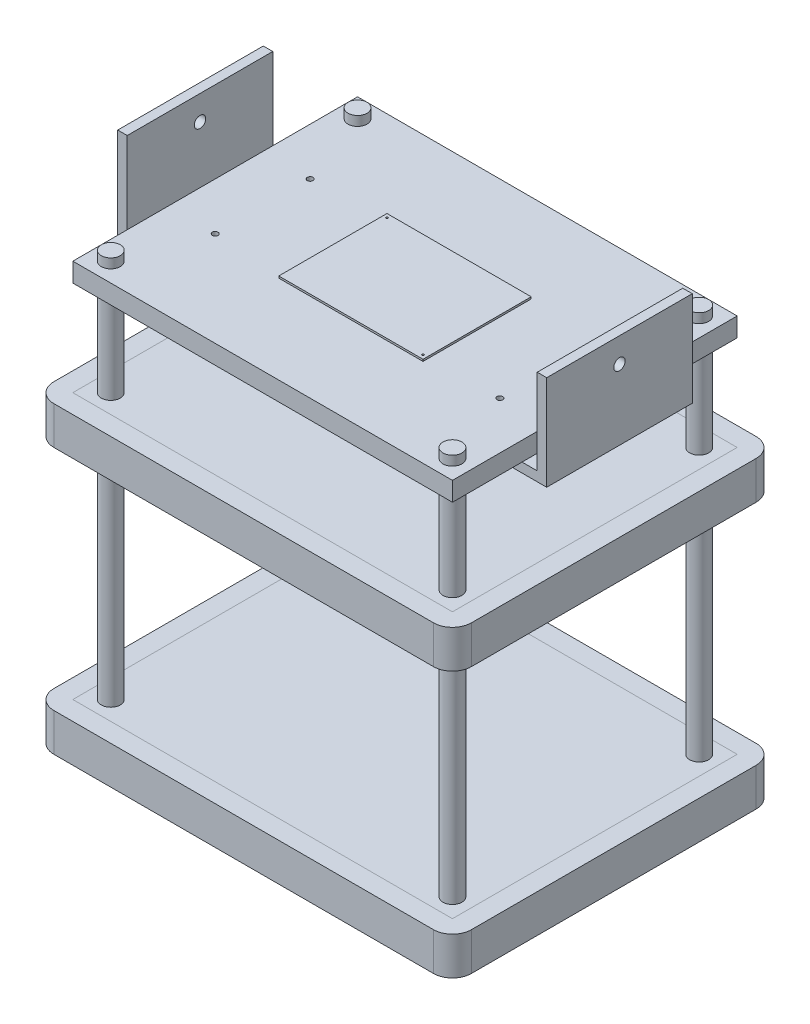
SolidWorks part; units mm, degrees
ref_plane "Front Plane" through (0, 0, 0) normal (0, 0, 1) x (1, 0, 0)
ref_plane "Top Plane" through (0, 0, 0) normal (0, 1, 0) x (1, 0, 0)
ref_plane "Right Plane" through (0, 0, 0) normal (1, 0, 0) x (0, 0, -1)
sketch "Sketch1" plane through (0, 0, 0) normal (0, 1, 0) x (1, 0, 0)
  line L1 (-100, 75) -> (100, 75)
  line L2 (-100, 75) -> (-100, -75)
  line L3 (-100, -75) -> (100, -75)
  line L4 (100, 75) -> (100, -75)
  line L5 (-100, 75) -> (100, -75) construction
  line L6 (-100, -75) -> (100, 75) construction
  point P0 (0, 0)
  dimension "D1" = 200
  dimension "D2" = 150
extrude "Boss-Extrude1" add sketch "Sketch1" along normal blind 10
sketch "Sketch2" plane through (0, 10, 0) normal (0, 1, 0) x (1, 0, 0)
  line L0 (-100, 75) -> (-100, -75) construction
  line L1 (100, 75) -> (-100, 75) construction
  line L2 (0, 73.0671) -> (0, 83.6614) construction
  line L3 (0, 83.6614) -> (0, -94.4748) construction
  line L4 (-110.8687, 0) -> (113.9791, 0) construction
  circle A0 centre (-90, 65) radius 5
  circle A1 centre (90, 65) radius 5
  circle A2 centre (90, -65) radius 5
  circle A3 centre (-90, -65) radius 5
  dimension "D1" = 10
  dimension "D2" = 10
  dimension "D3" = 10
extrude "Cut-Extrude1" cut sketch "Sketch2" against normal blind 10
ref_plane "Plane1" through (0, 140, 0) normal (0, 1, 0) x (1, 0, 0)
sketch "Sketch3" plane through (0, 140, 0) normal (0, 1, 0) x (1, 0, 0)
  line L1 (-100, 75) -> (100, 75)
  line L2 (-100, 75) -> (-100, -75)
  line L3 (-100, -75) -> (100, -75)
  line L4 (100, 75) -> (100, -75)
  line L5 (-100, 75) -> (100, -75) construction
  line L6 (-100, -75) -> (100, 75) construction
  circle A0 centre (-90, 65) radius 5
  circle A1 centre (90, 65) radius 5
  circle A2 centre (-90, -65) radius 5
  circle A3 centre (90, -65) radius 5
  point P0 (0, 0)
extrude "Boss-Extrude2" add sketch "Sketch3" along normal blind 10 separate body
ref_plane "Plane4" through (0, 200, 0) normal (0, 1, 0) x (1, 0, 0)
sketch "Sketch4" plane through (0, 200, 0) normal (0, 1, 0) x (1, 0, 0)
  line L1 (-100, 75) -> (100, 75)
  line L2 (-100, 75) -> (-100, -75)
  line L3 (-100, -75) -> (100, -75)
  line L4 (100, 75) -> (100, -75)
  line L5 (-100, 75) -> (100, -75) construction
  line L6 (-100, -75) -> (100, 75) construction
  circle A0 centre (-90, 65) radius 5
  circle A1 centre (90, 65) radius 5
  circle A2 centre (90, -65) radius 5
  circle A3 centre (-90, -65) radius 5
  point P1 (0, 0)
extrude "Boss-Extrude3" add sketch "Sketch4" along normal blind 10 separate body
sketch "Sketch5" plane through (0, 210, 0) normal (0, 1, 0) x (1, 0, 0)
  circle A0 centre (-90, -65) radius 5
sketch "Sketch17" plane through (0, 200, 0) normal (0, -1, 0) x (1, 0, 0)
  circle A0 centre (-90, -65) radius 5.3637
sketch "Sketch21" plane through (0, 10, 0) normal (0, 1, 0) x (1, 0, 0)
  circle A0 centre (-90, -65) radius 5
  circle A1 centre (-90, 65) radius 5
  circle A2 centre (90, 65) radius 5
  circle A3 centre (90, -65) radius 5
  dimension "D1" = 10
  dimension "D2" = 10
  dimension "D3" = 10
  dimension "D4" = 10
extrude "Boss-Extrude13" add sketch "Sketch21" along normal blind 205
sketch "Sketch22" plane through (0, 10, 0) normal (0, 1, 0) x (1, 0, 0)
  circle A0 centre (-90, 65) radius 5
  circle A1 centre (-90, -65) radius 5
  circle A2 centre (90, -65) radius 5
  circle A3 centre (90, 65) radius 5
  dimension "D1" = 10
  dimension "D2" = 10
  dimension "D3" = 10
  dimension "D4" = 10
extrude "Boss-Extrude14" add sketch "Sketch22" against normal blind 15
sketch "Sketch23" plane through (0, 210, 0) normal (0, 1, 0) x (1, 0, 0)
  line L0 (-100, 75) -> (-100, -75) construction
  line L1 (-140.155, 0) -> (119.4256, 0) construction
  line L2 (0, -82.5) -> (0, 82.5) construction
  circle A0 centre (-75, 25) radius 1.5
  circle A1 centre (-75, -25) radius 1.5
  circle A2 centre (75, -25) radius 1.5
  circle A3 centre (75, 25) radius 1.5
  dimension "D1" = 3
  dimension "D2" = 25
  dimension "D3" = 25
extrude "Cut-Extrude2" cut sketch "Sketch23" against normal blind 10
sketch "Sketch27" plane through (0, 210, 0) normal (0, 1, 0) x (1, 0, 0)
  line L0 (-38, 28.5) -> (38, -28.5) construction
  line L5 (-38, -28.5) -> (38, 28.5) construction
  line L7 (-38, 28.5) -> (38, 28.5)
  line L8 (-38, 28.5) -> (-38, -28.5)
  line L9 (-38, -28.5) -> (38, -28.5)
  line L10 (38, 28.5) -> (38, -28.5)
  circle A0 centre (-36, 26.5) radius 0.5
  circle A1 centre (36, -26.5) radius 0.5
  point P0 (-6.164, -10.787)
  point P5 (0, 0)
  point P11 (0, 0)
  dimension "D3" = 1
  dimension "D6" = 1
  dimension "D1" = 57
  dimension "D2" = 76
  dimension "D4" = 2
  dimension "D5" = 2
  dimension "D7" = 2
  dimension "D8" = 2
extrude "Boss-Extrude16" add sketch "Sketch27" along normal blind 1 contours L8 L7 L10 L9
sketch "Sketch30" plane through (0, 211, 0) normal (0, 1, 0) x (1, 0, 0)
  line L0 (-38, 28.5) -> (-38, -28.5) construction
  line L1 (-38, 28.5) -> (38, 28.5) construction
  line L2 (38, 28.5) -> (38, -28.5) construction
  line L3 (-38, -28.5) -> (38, -28.5) construction
  circle A0 centre (-36, 26.5) radius 0.5
  circle A1 centre (36, -26.5) radius 0.5
  dimension "D1" = 1
  dimension "D4" = 1
  dimension "D2" = 2
  dimension "D3" = 2
  dimension "D5" = 2
  dimension "D6" = 2
extrude "Cut-Extrude3" cut sketch "Sketch30" against normal blind 30
sketch "Sketch35" plane through (0, 0, 0) normal (0, -1, 0) x (-1, 0, 0)
  line L1 (100, -75) -> (-100, -75)
  line L2 (100, -75) -> (100, 75)
  line L3 (100, 75) -> (-100, 75)
  line L4 (-100, -75) -> (-100, 75)
  line L5 (100, -75) -> (-100, 75) construction
  line L6 (100, 75) -> (-100, -75) construction
  line L7 (110, -85) -> (-110, -85)
  line L8 (110, -85) -> (110, 85)
  line L9 (110, 85) -> (-110, 85)
  line L10 (-110, -85) -> (-110, 85)
  line L11 (110, -85) -> (-110, 85) construction
  line L12 (110, 85) -> (-110, -85) construction
  point P0 (0, 0)
  point P6 (0, 0)
  dimension "D1" = 150
  dimension "D2" = 170
  dimension "D3" = 200
  dimension "D4" = 220
extrude "Boss-Extrude19" add sketch "Sketch35" along normal mid plane 20 separate body
fillet "Fillet4" radius 10 4 edges at (110, 0, 85) (110, 0, -85) (-110, 0, 85) (-110, 0, -85)
sketch "Sketch39" plane through (0, 140, 0) normal (0, -1, 0) x (1, 0, 0)
  line L1 (-100, 75) -> (100, 75)
  line L2 (-100, 75) -> (-100, -75)
  line L3 (-100, -75) -> (100, -75)
  line L4 (100, 75) -> (100, -75)
  line L5 (-100, 75) -> (100, -75) construction
  line L6 (-100, -75) -> (100, 75) construction
  line L7 (-110, 85) -> (110, 85)
  line L8 (-110, 85) -> (-110, -85)
  line L9 (-110, -85) -> (110, -85)
  line L10 (110, 85) -> (110, -85)
  line L11 (-110, 85) -> (110, -85) construction
  line L12 (-110, -85) -> (110, 85) construction
  point P0 (0, 0)
  point P6 (0, 0)
  dimension "D1" = 150
  dimension "D2" = 200
  dimension "D3" = 170
  dimension "D4" = 220
extrude "Boss-Extrude20" add sketch "Sketch39" along normal mid plane 20 separate body
fillet "Fillet5" radius 10 4 edges at (110, 140, 85) (110, 140, -85) (-110, 140, -85) (-110, 140, 85)
sketch "Sketch42" plane through (0, 200, 0) normal (0, -1, 0) x (1, 0, 0)
  line L1 (-7.5, 10) -> (7.5, 10)
  line L2 (-7.5, 10) -> (-7.5, -10)
  line L3 (-7.5, -10) -> (7.5, -10)
  line L4 (7.5, 10) -> (7.5, -10)
  line L5 (-7.5, 10) -> (7.5, -10) construction
  line L6 (-7.5, -10) -> (7.5, 10) construction
  line L7 (-70.7403, -17.1967) -> (-45.7403, -17.1967)
  line L8 (-70.7403, -17.1967) -> (-70.7403, 32.8033)
  line L9 (-70.7403, 32.8033) -> (-45.7403, 32.8033)
  line L10 (-45.7403, -17.1967) -> (-45.7403, 32.8033)
  line L11 (-70.7403, -17.1967) -> (-45.7403, 32.8033) construction
  line L12 (-70.7403, 32.8033) -> (-45.7403, -17.1967) construction
  line L13 (15.7, 23.8618) -> (59, 23.8618)
  line L14 (15.7, 23.8618) -> (15.7, -19.4382)
  line L15 (15.7, -19.4382) -> (59, -19.4382)
  line L16 (59, 23.8618) -> (59, -19.4382)
  line L17 (15.7, 23.8618) -> (59, -19.4382) construction
  line L18 (15.7, -19.4382) -> (59, 23.8618) construction
  point P0 (0, 0)
  point P6 (-58.2403, 7.8033)
  point P11 (37.35, 2.2118)
  dimension "D1" = 20
  dimension "D2" = 15
  dimension "D3" = 50
  dimension "D4" = 25
  dimension "D5" = 43.3
  dimension "D6" = 43.3
  dimension "D7" = 8.2
extrude "Boss-Extrude23" add sketch "Sketch42" along normal blind 1
sketch "Sketch46" plane through (0, 200, 0) normal (0, -1, 0) x (-1, 0, 0)
  line L0 (-196.0871, 0) -> (303.0775, 0) construction
  line L5 (100, -75) -> (100, 75) construction
  line L6 (0, 93.5) -> (0, -93.5) construction
  line L7 (-108, 38.3353) -> (-108, -38.3353)
  line L8 (78, 38.3353) -> (108, 38.3353)
  line L9 (78, 38.3353) -> (78, -38.3353)
  line L10 (78, -38.3353) -> (108, -38.3353)
  line L11 (108, 38.3353) -> (108, -38.3353)
  line L12 (78, 38.3353) -> (108, -38.3353) construction
  line L13 (78, -38.3353) -> (108, 38.3353) construction
  line L14 (-78, -38.3353) -> (-108, -38.3353)
  line L15 (-78, 38.3353) -> (-78, -38.3353)
  line L16 (-78, 38.3353) -> (-108, 38.3353)
  point P0 (122.8294, -19.1676)
  point P6 (93, 0)
  dimension "D1" = 22
  dimension "D2" = 30
extrude "Boss-Extrude24" add sketch "Sketch46" along normal blind 5
sketch "Sketch48" plane through (-108, 0, 0) normal (-1, 0, 0) x (0, 0, 1)
  line L1 (-38.3353, 195) -> (38.3353, 195)
  line L2 (-38.3353, 195) -> (-38.3353, 245)
  line L3 (-38.3353, 245) -> (38.3353, 245)
  line L4 (38.3353, 195) -> (38.3353, 245)
  dimension "D1" = 50
extrude "Boss-Extrude25" add sketch "Sketch48" along normal blind 5
sketch "Sketch49" plane through (-113, 0, 0) normal (-1, 0, 0) x (0, 0, 1)
  line L1 (-38.3353, 195) -> (38.3353, 195) construction
  circle A0 centre (0, 232) radius 3
  dimension "D2" = 6
  dimension "D1" = 37
extrude "Cut-Extrude4" cut sketch "Sketch49" against normal blind 5
sketch "Sketch54" plane through (108, 0, 0) normal (1, 0, 0) x (0, 0, -1)
  line L1 (-38.3353, 195) -> (38.3353, 195)
  line L2 (-38.3353, 195) -> (-38.3353, 245)
  line L3 (-38.3353, 245) -> (38.3353, 245)
  line L4 (38.3353, 195) -> (38.3353, 245)
extrude "Boss-Extrude26" add sketch "Sketch54" along normal blind 5
sketch "Sketch55" plane through (113, 0, 0) normal (1, 0, 0) x (0, 0, -1)
  line L0 (-38.3353, 195) -> (38.3353, 195) construction
  circle A0 centre (0, 232) radius 3
  dimension "D1" = 6
  dimension "D2" = 37
extrude "Cut-Extrude5" cut sketch "Sketch55" against normal blind 5
